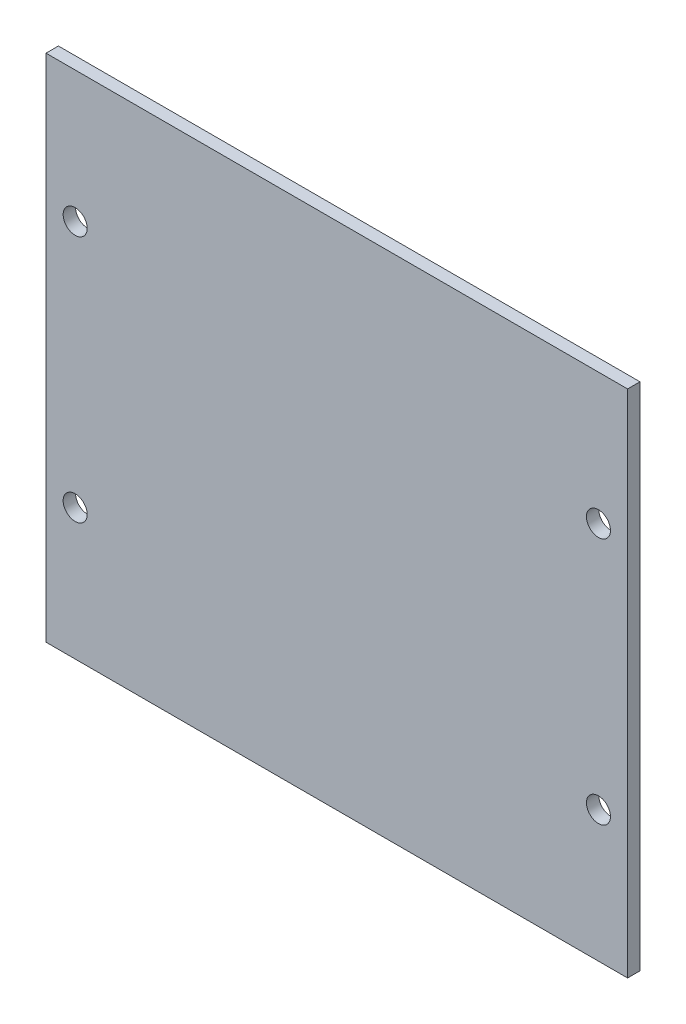
SolidWorks part; units mm, degrees
ref_plane "Front Plane" through (0, 0, 0) normal (0, 0, 1) x (1, 0, 0)
ref_plane "Top Plane" through (0, 0, 0) normal (0, 1, 0) x (1, 0, 0)
ref_plane "Right Plane" through (0, 0, 0) normal (1, 0, 0) x (0, 0, -1)
sketch "Sketch1" plane through (0, 0, 0) normal (0, 0, 1) x (1, 0, 0)
  line L0 (0, 36.4012) -> (0, -36.799) construction
  line L1 (-73.2002, 0) -> (87.9197, 0) construction
  line L2 (27.5, -13.95) -> (27.5, -11.45)
  line L3 (-39.9, 35) -> (39.9, 35)
  line L4 (-39.9, 35) -> (-39.9, -35)
  line L5 (-39.9, -35) -> (39.9, -35)
  line L6 (39.9, 35) -> (39.9, -35)
  line L7 (-27.5, 13.95) -> (27.5, 13.95)
  line L8 (-27.5, 13.95) -> (-27.5, 11.45)
  line L9 (-27.5, 11.45) -> (27.5, 11.45)
  line L10 (27.5, 13.95) -> (27.5, 11.45)
  line L15 (-27.5, -13.95) -> (27.5, -13.95)
  line L16 (-27.5, -13.95) -> (-27.5, -11.45)
  line L17 (-27.5, -11.45) -> (27.5, -11.45)
  line L18 (27.5, -18.95) -> (27.5, -16.45)
  line L19 (-27.5, 18.95) -> (27.5, 18.95)
  line L20 (-27.5, 18.95) -> (-27.5, 16.45)
  line L21 (-27.5, 16.45) -> (27.5, 16.45)
  line L22 (27.5, 18.95) -> (27.5, 16.45)
  line L23 (-27.5, -18.95) -> (27.5, -18.95)
  line L24 (-27.5, -18.95) -> (-27.5, -16.45)
  line L25 (-27.5, -16.45) -> (27.5, -16.45)
  circle A0 centre (-35.9, 17) radius 1.65
  circle A1 centre (35.9, 17) radius 1.65
  circle A2 centre (35.9, -17) radius 1.65
  circle A3 centre (-35.9, -17) radius 1.65
  point P13 (-27.5, 12.7)
  dimension "D7" = 3.3
  dimension "D1" = 79.8
  dimension "D2" = 70
  dimension "D3" = 2.5
  dimension "D4" = 55
  dimension "D5" = 25.4
  dimension "D6" = 2.5
  dimension "D8" = 4
  dimension "D9" = 18
extrude "Boss-Extrude1" add sketch "Sketch1" along normal blind 1.7 contours L4 L5 L6 L3
extrude "Boss-Extrude2" add sketch "Sketch1<3>" against normal blind 9.5 contours L9 L10 L7 L8 | L17 L2 L15 L16 | L19 L22 L21 L20 | L24 L25 L18 L23
sketch "Sketch1<3>" plane through (0, 0, 0) normal (0, 0, 1) x (1, 0, 0) same geometry as "Sketch1"
extrude "Cut-Extrude1" cut sketch "Sketch1<4>" along normal through all contours A1 | A2 | A0 | A3
sketch "Sketch1<4>" plane through (0, 0, 0) normal (0, 0, 1) x (1, 0, 0) same geometry as "Sketch1"
